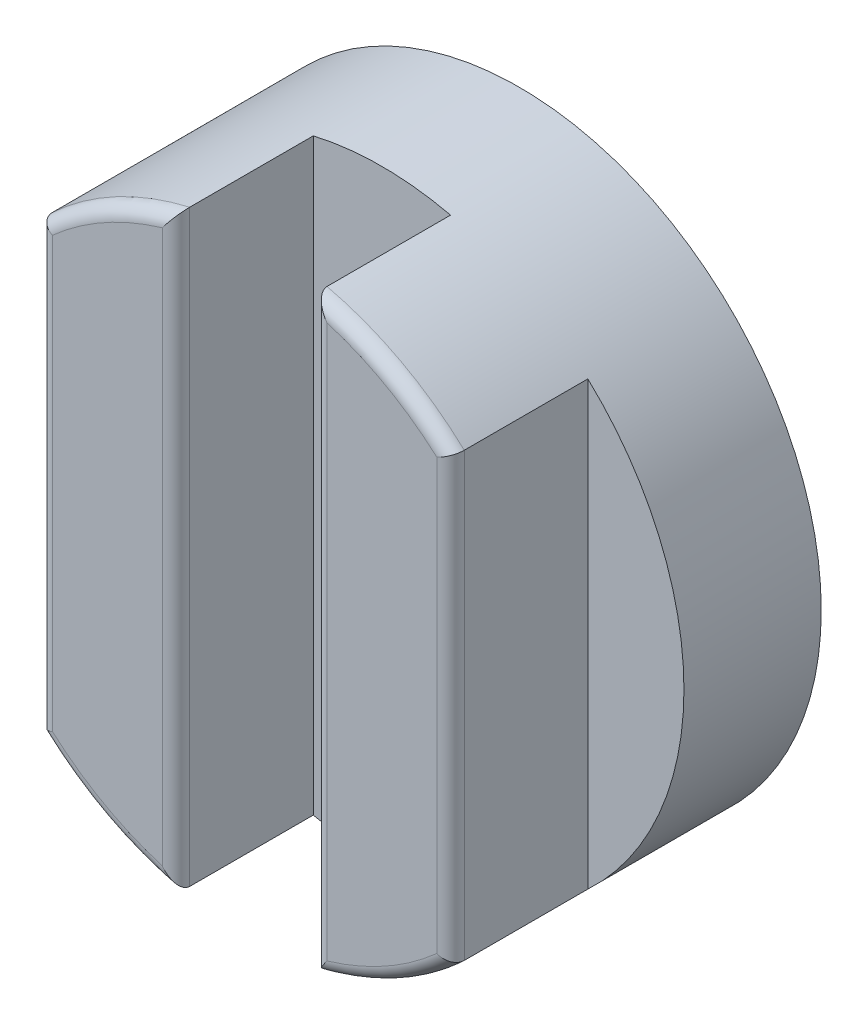
SolidWorks part; units mm, degrees
ref_plane "Plan de face" through (0, 0, 0) normal (0, 0, 1) x (1, 0, 0)
ref_plane "Plan de dessus" through (0, 0, 0) normal (0, 1, 0) x (1, 0, 0)
ref_plane "Plan de droite" through (0, 0, 0) normal (1, 0, 0) x (0, 0, -1)
sketch "Esquisse1" plane through (0, 0, 0) normal (0, 0, 1) x (1, 0, 0)
  circle A0 centre (0, 0) radius 11
  dimension "D1" = 22
extrude "Boss.-Extru.1" add sketch "Esquisse1" along normal blind 5
sketch "Esquisse2" plane through (0, 0, 5) normal (0, 0, 1) x (1, 0, 0)
  line L0 (0, 5.7045) -> (0, -6.8994) construction
  line L1 (-7.5, 8.0467) -> (-7.5, -8.0467)
  line L2 (-2.5, 10.7121) -> (-2.5, -10.7121)
  line L3 (7.5, 8.0467) -> (7.5, -8.0467)
  line L4 (2.5, 10.7121) -> (2.5, -10.7121)
  circle A0 centre (0, 0) radius 11 construction
  arc A1 (-2.5, -10.7121) -> (2.5, -10.7121) centre (0, 0) ccw
  arc A2 (2.5, 10.7121) -> (-2.5, 10.7121) centre (0, 0) ccw
  circle A3 centre (0, 0) radius 11
  circle M1 centre (0, 0) radius 11
  dimension "D1" = 5
  dimension "D2" = 5
extrude "Boss.-Extru.3" add sketch "Esquisse2" along normal blind 5 contours L2 L1 M1 | L4 L3 M1 region at (-4.8871, 0, 5) region at (4.8871, 0, 5)
fillet "Congé3" radius 0.5 8 edges at (5.1746, 9.7069, 10) (7.5, 0, 10) (2.5, 0, 10) (5.1746, -9.7069, 10) (-5.1746, -9.7069, 10) (-2.5, 0, 10) (-5.1746, 9.7069, 10) (-7.5, 0, 10)
